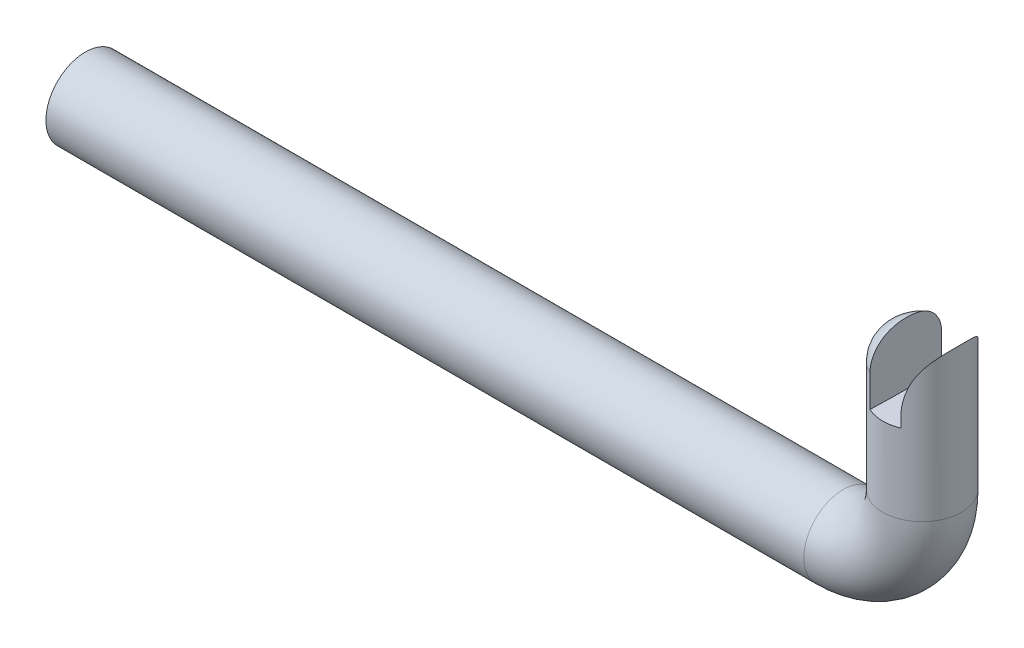
SolidWorks part; units mm, degrees
ref_plane "Front Plane" through (0, 0, 0) normal (0, 0, 1) x (1, 0, 0)
ref_plane "Top Plane" through (0, 0, 0) normal (0, 1, 0) x (1, 0, 0)
ref_plane "Right Plane" through (0, 0, 0) normal (1, 0, 0) x (0, 0, -1)
sketch "Sketch1" plane through (0, 0, 0) normal (1, 0, 0) x (0, 0, -1)
  circle A0 centre (0, 0) radius 3.175
  dimension "D1" = 6.35
sketch "Sketch2" plane through (0, 0, 0) normal (0, 0, 1) x (1, 0, 0)
  line L0 (0, 0) -> (60.96, 0)
  line L1 (67.31, 6.35) -> (67.31, 12.7)
  arc A0 (60.96, 0) -> (67.31, 6.35) centre (60.96, 6.35) ccw
  point P6 (67.31, 0)
  dimension "D3" = 6.35
  dimension "D1" = 67.31
  dimension "D2" = 12.7
sweep "Sweep3" add profiles "Sketch1" path "Sketch2"
sketch "Sketch3" plane through (0, 12.7, 0) normal (0, 1, 0) x (1, 0, 0)
  arc A0 (65.9895, 2.8874) -> (65.9895, -2.8874) centre (67.31, 0) ccw
  arc A1 (65.9895, -2.8874) -> (65.9895, 2.8874) centre (-16.51, 0) ccw
  circle A2 centre (-16.51, 0) radius 82.55 construction
  dimension "D1" = 3.175
extrude "Boss-Extrude1" add sketch "Sketch3" along normal blind 5.08
sketch "Sketch4" plane through (0, 12.7, 0) normal (0, 1, 0) x (1, 0, 0)
  arc A0 (68.5295, -2.9315) -> (68.5295, 2.9315) centre (67.31, 0) ccw
  arc A1 (68.5295, 2.9315) -> (68.5295, -2.9315) centre (-16.51, 0) cw
  circle A2 centre (-16.51, 0) radius 85.09 construction
  dimension "D1" = 3.175
extrude "Boss-Extrude2" add sketch "Sketch4" along normal up to surface (1.0867 mm away)
fillet "Fillet1" radius 2.54 1 edges at (64.135, 17.78, 0)
